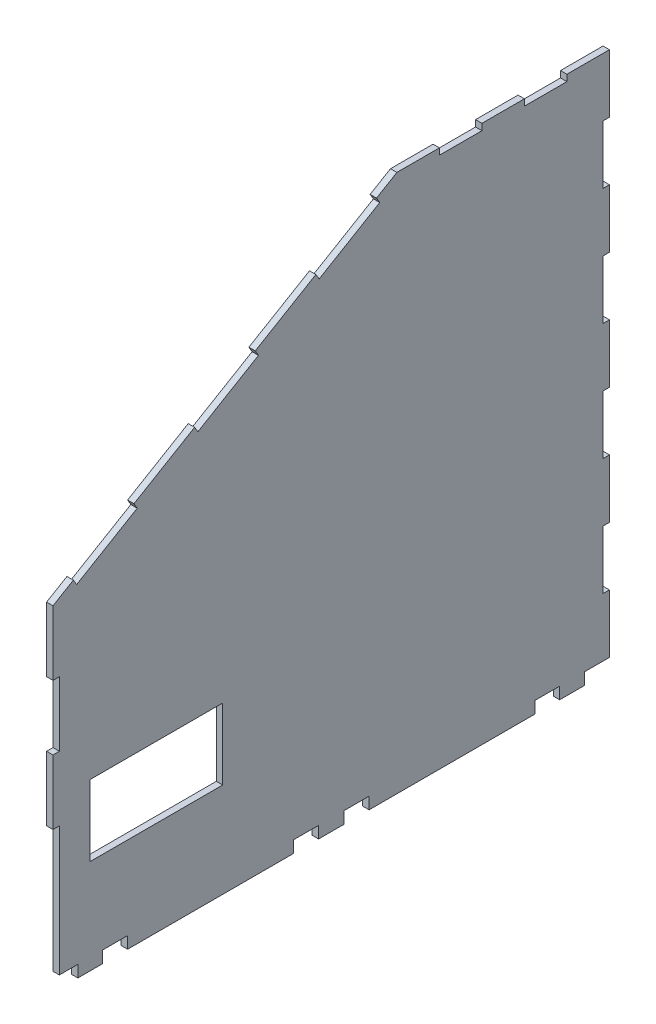
SolidWorks part; units mm, degrees
ref_plane "Ön Düzlem" through (0, 0, 0) normal (0, 0, 1) x (1, 0, 0)
ref_plane "Üst Düzlem" through (0, 0, 0) normal (0, 1, 0) x (1, 0, 0)
ref_plane "Sağ Düzlem" through (0, 0, 0) normal (1, 0, 0) x (0, 0, -1)
sketch "Sketch1" plane through (0, 0, 0) normal (1, 0, 0) x (0, 0, -1)
  line L0 (117.52, 112.5) -> (99.566, 112.5)
  line L6 (117.52, -109.8) -> (117.52, -85.1)
  line L13 (-107.0133, -112.5) -> (-107.0133, -114.8)
  line L14 (-6.4686, 92.2661) -> (-32.0795, 77.122)
  line L17 (27.75, 112.5) -> (19.1423, 107.4101)
  line L18 (-114.82, -109.8) -> (-107.0133, -109.8)
  line L20 (-107.0133, -114.8) -> (-96.5067, -114.8)
  line L21 (-86, -112.5) -> (-86, -114.8)
  line L22 (-114.82, -27.96) -> (-114.82, -0.68)
  line L23 (-117.52, -55.24) -> (-117.52, -27.96)
  line L24 (-96.5067, -114.8) -> (-96.5067, -112.5)
  line L25 (-117.52, -0.68) -> (-117.52, 26.6)
  line L26 (-117.52, -0.68) -> (-114.82, -0.68)
  line L27 (-117.52, -27.96) -> (-114.82, -27.96)
  line L28 (-114.82, -82.52) -> (-114.82, -55.24)
  line L29 (-117.52, -55.24) -> (-114.82, -55.24)
  line L31 (-86, -109.8) -> (-86, -112.5)
  line L32 (-107.0133, -109.8) -> (-107.0133, -112.5)
  line L33 (-96.5067, -109.8) -> (-96.5067, -112.5)
  line L34 (-96.5067, -109.8) -> (-86, -109.8)
  line L35 (-5.3333, -112.5) -> (-5.3333, -114.8)
  line L37 (-16, -112.5) -> (-16, -109.8)
  line L38 (-16, -109.8) -> (-5.3333, -109.8)
  line L39 (-5.3333, -114.8) -> (5.3333, -114.8)
  line L40 (-86, -114.8) -> (-16, -114.8)
  line L41 (5.3333, -109.8) -> (16, -109.8)
  line L42 (-5.3333, -109.8) -> (-5.3333, -112.5)
  line L43 (5.3333, -109.8) -> (5.3333, -112.5)
  line L44 (16, -109.8) -> (16, -112.5)
  line L45 (5.3333, -114.8) -> (5.3333, -112.5)
  line L46 (96.5067, -112.5) -> (96.5067, -114.8)
  line L47 (114.82, -35.7) -> (114.82, -11)
  line L48 (86, -109.8) -> (96.5067, -109.8)
  line L49 (96.5067, -114.8) -> (107.0133, -114.8)
  line L51 (86, -109.8) -> (86, -112.5)
  line L52 (96.5067, -109.8) -> (96.5067, -112.5)
  line L53 (107.0133, -109.8) -> (107.0133, -112.5)
  line L55 (107.0133, -109.8) -> (117.52, -109.8)
  line L56 (117.52, -60.4) -> (117.52, -35.7)
  line L57 (114.82, 13.7) -> (114.82, 38.4)
  line L58 (117.52, -11) -> (117.52, 13.7)
  line L59 (114.82, 63.1) -> (114.82, 87.8)
  line L60 (117.52, 38.4) -> (117.52, 63.1)
  line L61 (107.0133, -112.5) -> (107.0133, -114.8)
  line L62 (117.52, 87.8) -> (117.52, 112.5)
  line L63 (114.82, -85.1) -> (114.82, -60.4)
  line L64 (117.52, -85.1) -> (114.82, -85.1)
  line L65 (117.52, 13.7) -> (114.82, 13.7)
  line L66 (117.52, 87.8) -> (114.82, 87.8)
  line L67 (117.52, 63.1) -> (114.82, 63.1)
  line L68 (117.52, 38.4) -> (114.82, 38.4)
  line L69 (117.52, -11) -> (114.82, -11)
  line L70 (117.52, -35.7) -> (114.82, -35.7)
  line L71 (117.52, -60.4) -> (114.82, -60.4)
  line L72 (-57.6905, 61.978) -> (-83.3014, 46.8339)
  line L73 (-5.0944, 89.942) -> (-6.4686, 92.2661)
  line L74 (-107.538, 29.3658) -> (-81.9271, 44.5098)
  line L75 (-16, -114.8) -> (-16, -112.5)
  line L76 (99.566, 109.8) -> (81.612, 109.8)
  line L77 (16, -112.5) -> (16, -114.8)
  line L78 (63.658, 109.8) -> (45.704, 109.8)
  line L79 (-108.9123, 31.6899) -> (-117.52, 26.6)
  line L80 (45.704, 109.8) -> (45.704, 112.5)
  line L81 (63.658, 109.8) -> (63.658, 112.5)
  line L82 (81.612, 109.8) -> (81.612, 112.5)
  line L83 (99.566, 109.8) -> (99.566, 112.5)
  line L84 (16, -114.8) -> (86, -114.8)
  line L85 (86, -114.8) -> (86, -112.5)
  line L86 (-55.82, -44.8) -> (-45.82, -44.8)
  line L87 (-108.9123, 31.6899) -> (-107.538, 29.3658)
  line L88 (19.1423, 107.4101) -> (20.5165, 105.086)
  line L89 (-56.3162, 59.6539) -> (-30.7053, 74.7979)
  line L90 (-45.82, -44.8) -> (-45.82, -74.8)
  line L91 (-5.0944, 89.942) -> (20.5165, 105.086)
  line L92 (-30.7053, 74.7979) -> (-32.0795, 77.122)
  line L93 (-56.3162, 59.6539) -> (-57.6905, 61.978)
  line L94 (-81.9271, 44.5098) -> (-83.3014, 46.8339)
  line L95 (45.704, 112.5) -> (27.75, 112.5)
  line L96 (-45.82, -74.8) -> (-55.82, -74.8)
  line L97 (81.612, 112.5) -> (63.658, 112.5)
  line L98 (-114.82, -82.52) -> (-114.82, -109.8)
  line L99 (-101.82, -74.8) -> (-101.82, -44.8)
  line L103 (-114.82, -41.8) -> (-111.82, -41.8)
  line L109 (-101.82, -44.8) -> (-55.82, -44.8)
  line L114 (-55.82, -74.8) -> (-101.82, -74.8)
  point P0 (0, 0)
extrude "Boss-Extrude1" add sketch "Sketch1" along normal blind 2.7 contours L82 L97 L81 L78 L80 L95 L17 L88 L91 L73 L14 L92 L89 L93 L72 L94 L74 L87 L79 L25 L26 L22 L27 L23 L29 L28 L18 L32 L33 L34 L31 L37 L38 L42 L43 L41 L44 L51 L48 L52 L53 region at (0, -10.4384, -12.475)
ref_plane "Plane1" through (2.7, 112.5, -27.75) normal (0, -0.509, 0.8608) x (1, 0, 0)
sketch "Sketch2" plane through (2.7, 112.5, -27.75) normal (0, -0.509, 0.8608) x (1, 0, 0)
